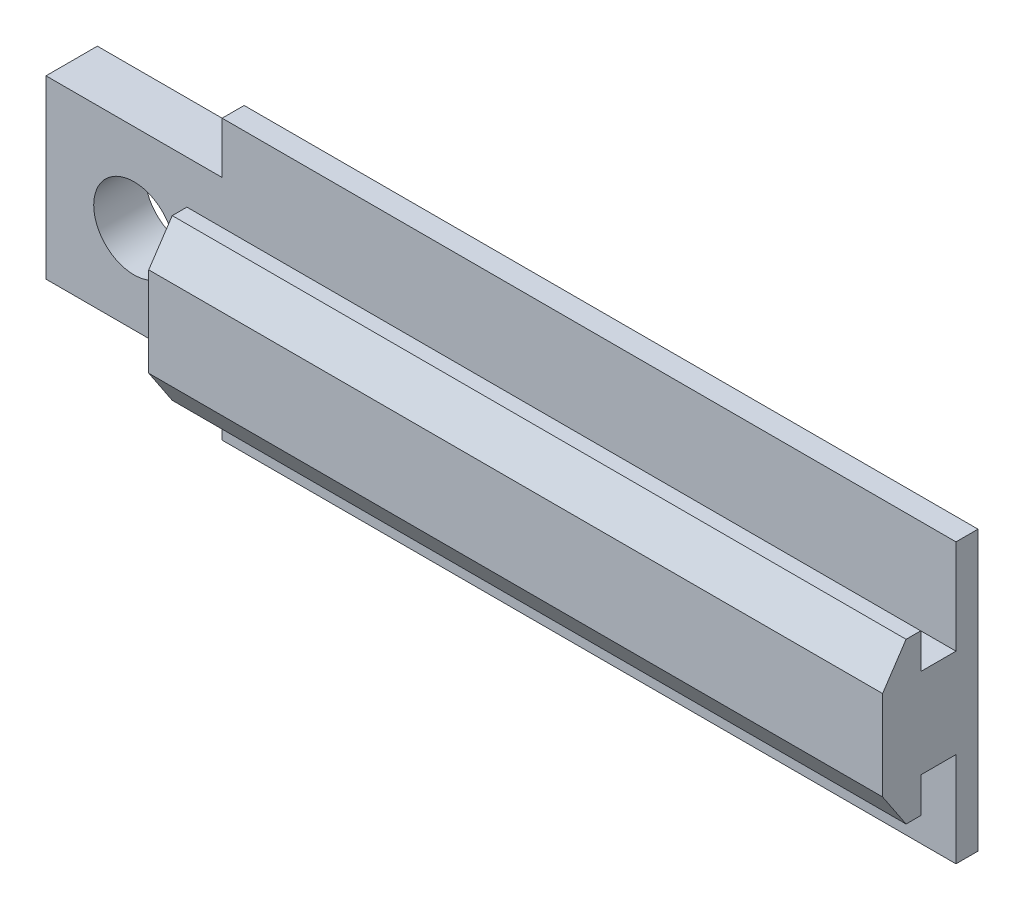
SolidWorks part; units mm, degrees
ref_plane "Front Plane" through (0, 0, 0) normal (0, 0, 1) x (1, 0, 0)
ref_plane "Top Plane" through (0, 0, 0) normal (0, 1, 0) x (1, 0, 0)
ref_plane "Right Plane" through (0, 0, 0) normal (1, 0, 0) x (0, 0, -1)
sketch "Sketch1" plane through (0, 0, 0) normal (0, 1, 0) x (1, 0, 0)
  line L1 (-25, 3.25) -> (25, 3.25)
  line L2 (-25, 3.25) -> (-25, -3.25)
  line L3 (-25, -3.25) -> (25, -3.25)
  line L4 (25, 3.25) -> (25, -3.25)
  line L5 (-25, 3.25) -> (25, -3.25) construction
  line L6 (-25, -3.25) -> (25, 3.25) construction
  point P0 (0, 0)
  dimension "D1" = 50
  dimension "D2" = 6.5
extrude "Boss-Extrude1" add sketch "Sketch1" along normal blind 19
sketch "Sketch2" plane through (25, 0, 0) normal (1, 0, 0) x (0, 0, -1)
  line L0 (-3.25, 9.5) -> (1.75, 9.5) construction
  line L1 (-3.25, 19) -> (-3.25, 0) construction
  line L2 (1.75, 12.55) -> (1.75, 6.45) construction
  line L3 (1.75, 12.55) -> (-0.65, 12.55)
  line L4 (1.75, 6.45) -> (-0.65, 6.45)
  line L5 (-0.65, 12.55) -> (-0.65, 14.95)
  line L6 (-0.65, 14.95) -> (-1.65, 14.95)
  line L7 (-0.65, 6.45) -> (-0.65, 4.05)
  line L8 (-0.65, 4.05) -> (-1.65, 4.05)
  line L9 (1.75, 12.55) -> (1.75, 19)
  line L10 (-3.25, 19) -> (3.25, 19) construction
  line L11 (1.75, 6.45) -> (1.75, 0)
  line L12 (-3.25, 0) -> (3.25, 0) construction
  line L13 (-0.65, 12.55) -> (-3.25, 12.55) construction
  line L14 (-1.65, 14.95) -> (-3.25, 12.55)
  line L15 (-0.65, 6.45) -> (-3.25, 6.45) construction
  line L16 (-1.65, 4.05) -> (-3.25, 6.45)
  line L17 (-3.25, 6.45) -> (-3.25, 12.55)
  point P7 (1.75, 9.5)
  point P8 (-3.25, 9.5)
  dimension "D1" = 5
  dimension "D2" = 6.1
  dimension "D3" = 2.4
  dimension "D4" = 2.4
  dimension "D5" = 1
extrude "Cut-Extrude1" cut sketch "Sketch2" along direction (-1, 0, 0) on the side against the normal through all and the other way through all
sketch "Sketch3" plane through (-25, 0, 0) normal (-1, 0, 0) x (0, 0, 1)
  line L6 (-1.75, 12.55) -> (-1.75, 6.45) construction
  line L7 (-1.75, 9.5) -> (-3.5, 9.5) construction
  line L9 (-5.25, 15.5) -> (-1.75, 15.5)
  line L10 (-5.25, 15.5) -> (-5.25, 3.5)
  line L11 (-5.25, 3.5) -> (-1.75, 3.5)
  line L12 (-1.75, 15.5) -> (-1.75, 3.5)
  line L13 (-5.25, 15.5) -> (-1.75, 3.5) construction
  line L14 (-5.25, 3.5) -> (-1.75, 15.5) construction
  point P4 (0, 0)
  point P9 (0, 0)
  point P10 (0, 0)
  point P11 (0, 0)
  dimension "D1" = 12
  dimension "D2" = 3.5
extrude "Boss-Extrude2" add sketch "Sketch3" along normal blind 12
sketch "Sketch4" plane through (0, 0, -5.25) normal (0, 0, -1) x (-1, 0, 0)
  line L0 (31, 9.5) -> (37, 9.5) construction
  line L1 (37, 15.5) -> (37, 3.5) construction
  line L2 (31, 9.5) -> (31, 3.5) construction
  line L3 (37, 3.5) -> (25, 3.5) construction
  circle A0 centre (31, 9.5) radius 2.75
  dimension "D1" = 5.5
extrude "Cut-Extrude2" cut sketch "Sketch4" against normal up to next contours A0
